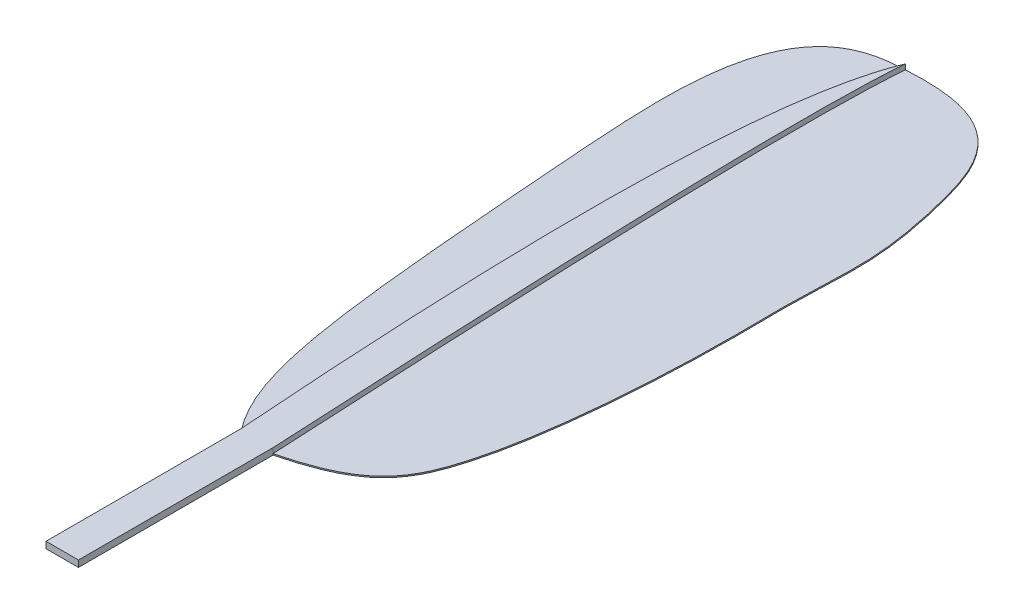
SolidWorks part; units mm, degrees
ref_plane "Front Plane" through (0, 0, 0) normal (0, 0, 1) x (1, 0, 0)
ref_plane "Top Plane" through (0, 0, 0) normal (0, 1, 0) x (1, 0, 0)
ref_plane "Right Plane" through (0, 0, 0) normal (1, 0, 0) x (0, 0, -1)
sketch "Sketch2" plane through (0, 0, 0) normal (0, 1, 0) x (1, 0, 0)
  line L0 (0, 0) -> (0, 100) construction
  line L1 (0, 0) -> (0, -30) construction
  line L3 (-2.5, 0) -> (2.5, 0) construction
  line L4 (-2.5, 0) -> (-2.5, -30)
  line L5 (-2.5, -30) -> (2.5, -30)
  line L6 (2.5, 0) -> (2.5, -30)
  spline S0 degree 3 poles (2.5, 0) (12.9342, 2.6311) (20.6225, 11.7076) (22.5547, 44.543) (22.0049, 67.1718) (23.8109, 72.5918) (16.9191, 98.0712) (8.9424, 100.5671) (0, 100) knots 0 0 0 0 0.1561 0.394681 0.460941 0.752435 0.809985 1 1 1 1
  spline S1 degree 2 poles (2.5, 0) (-1.6392, 79.8302) (0, 100) knots 0 0 0 1 1 1
  spline S2 degree 2 poles (-2.5, 0) (-8.3315, 79.8852) (0, 100) knots 0 0 0 1 1 1
  spline S3 degree 3 poles (0, 100) (-7.3575, 99.7562) (-16.6394, 96.1727) (-11.3377, 24.2277) (-9.5577, 8.3833) (-2.5, 0) knots 0 0 0 0 0.313532 0.413532 1 1 1 1
  point P10 (10.0606, 113.4257)
  point P12 (18.1675, 54.0195)
  point P14 (14.1805, 111.4322)
  point P15 (21.8887, 54.2853)
  point P16 (18.6991, 104.6543)
  point P17 (-9.2099, 84.3207)
  point P18 (17.0242, 102.9111)
  point P19 (13.9343, 105.0043)
  point P20 (15.8281, 105.0043)
  point P21 (17.2236, 95.9339)
  point P22 (17.9213, 91.6478)
  point P23 (22.307, 54.3694)
  point P24 (18.1478, 109.8169)
  point P25 (-15.7697, 96.1098)
  point P26 (-18.0709, 92.7081)
  point P27 (18.7481, 110.2171)
  point P28 (19.0483, 91.5075)
  point P29 (-14.6692, 73.5982)
  point P30 (19.3484, 88.706)
  point P31 (-14.7692, 72.8978)
  dimension "D1" = 5
  dimension "40" = 30
  dimension "160" = 100
extrude "Boss-Extrude1" add sketch "Sketch2" along normal blind 1 contours S2 L4 L5 L6 S1 region at (-1.2617, 0, -28.3155)
extrude "Boss-Extrude2" add sketch "Sketch2<4>" along normal blind 0.2 contours S1 S0 | S2 S3 region at (-8.2708, 0, -57.525) region at (10.4905, 0, -52.5807)
sketch "Sketch2<4>" plane through (0, 0, 0) normal (0, 1, 0) x (1, 0, 0) same geometry as "Sketch2"
